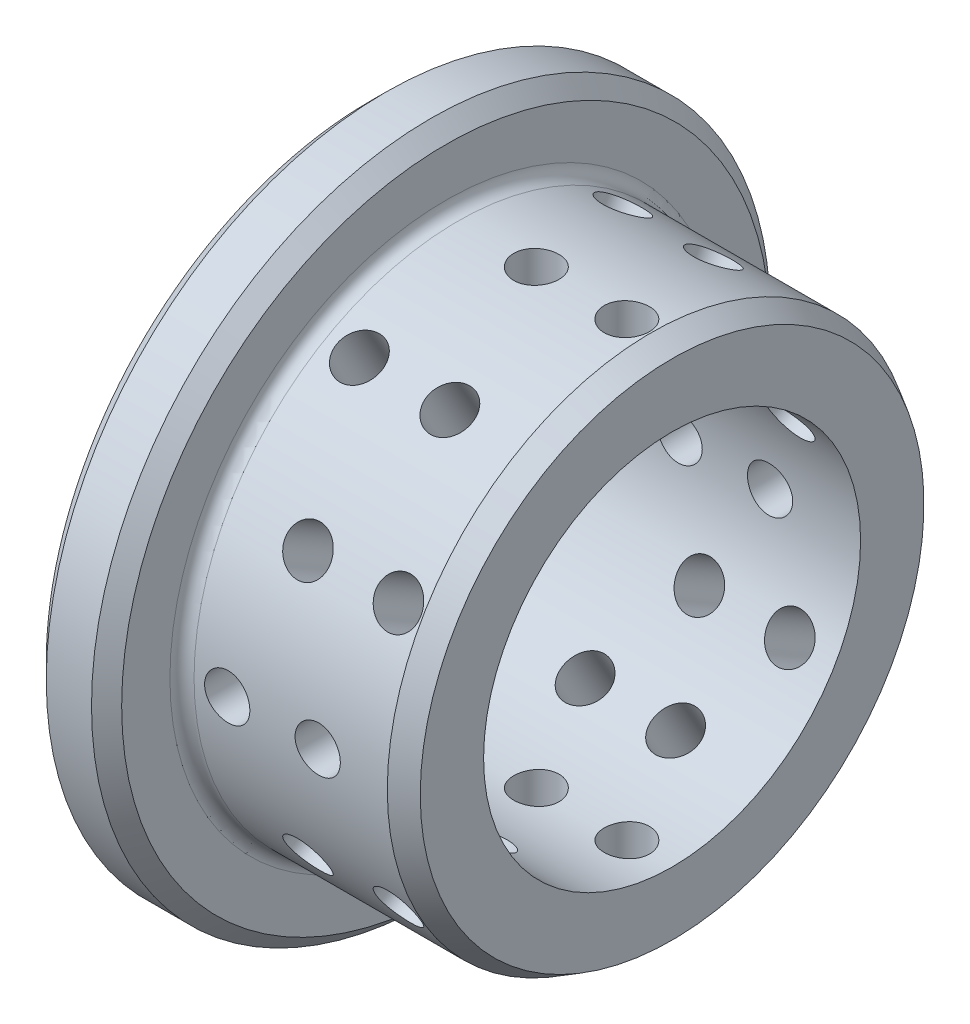
SolidWorks part; units mm, degrees
material "Cast Alloy Steel"
ref_plane "Front Plane" through (0, 0, 0) normal (0, 0, 1) x (1, 0, 0)
ref_plane "Top Plane" through (0, 0, 0) normal (0, 1, 0) x (1, 0, 0)
ref_plane "Right Plane" through (0, 0, 0) normal (1, 0, 0) x (0, 0, -1)
sketch "Sketch1" plane through (0, 0, 0) normal (0, 0, 1) x (1, 0, 0)
  line L0 (0, 0) -> (27.5999, 0) construction
  line L1 (0, 12.5) -> (0, 22.5)
  line L2 (0, 22.5) -> (5, 22.5)
  line L3 (5, 22.5) -> (5, 17.5)
  line L4 (5, 17.5) -> (20, 17.5)
  line L5 (20, 17.5) -> (20, 12.5)
  line L6 (20, 12.5) -> (0, 12.5)
  dimension "D1" = 45
  dimension "D2" = 35
  dimension "D3" = 25
  dimension "D4" = 5
  dimension "D5" = 15
revolve "Revolve1" add sketch "Sketch1" angle 360 about L0
sketch "Sketch2" plane through (0, 0, 0) normal (-1, 0, 0) x (0, 0, 1)
  circle A0 centre (0, 0) radius 20 construction
  circle A1 centre (0, 20) radius 1.5
  circle A2 centre (17.3205, 10) radius 1.5
  circle A3 centre (17.3205, -10) radius 1.5
  circle A4 centre (0, -20) radius 1.5
  circle A5 centre (-17.3205, -10) radius 1.5
  circle A6 centre (-17.3205, 10) radius 1.5
  point P17 (0, 0)
  dimension "D1" = 40
  dimension "D2" = 3
  dimension "D3" = 6
extrude "Cut-Extrude1" cut sketch "Sketch2" against normal blind 4 and the other way through all
sketch "Sketch3" plane through (0, 0, 0) normal (-1, 0, 0) x (0, 0, 1)
  line L0 (0, 0) -> (17, 0) construction
  circle A0 centre (0, 0) radius 17 construction
  circle A1 centre (17, 0) radius 1.5
  dimension "D1" = 34
  dimension "D2" = 3
extrude "Cut-Extrude2" cut sketch "Sketch3" against normal blind 4
pattern_circular "CirPattern1" count 6 over 360 about axis through (0, 0, 0) along (-1, 0, 0) of "Cut-Extrude2"
sketch "Sketch4" plane through (0, 0, 0) normal (0, 1, 0) x (1, 0, 0)
  line L0 (0, 0) -> (20, 0) construction
  line L1 (20, -17.5) -> (20, 17.5) construction
  circle A0 centre (11, 0) radius 1.5
  circle A1 centre (17, 0) radius 1.5
  dimension "D3" = 3
  dimension "D1" = 3
  dimension "D2" = 6
extrude "Cut-Extrude3" cut sketch "Sketch4" against normal up to surface (17.4356 mm away) up to face at (5, 0, 17.5)
sketch "Sketch5" plane through (0, 0, 0) normal (0, 0, 1) x (1, 0, 0)
  line L0 (0, 0) -> (20, 0) construction
  line L1 (20, -17.5) -> (20, 17.5) construction
  circle A0 centre (8, 0) radius 1.5
  circle A1 centre (14, 0) radius 1.5
  dimension "D2" = 3
  dimension "D1" = 8
  dimension "D3" = 6
extrude "Cut-Extrude4" cut sketch "Sketch5" against normal up to surface (17.5 mm away) up to face at (11.3388, -17.4389, -1.4612)
pattern_circular "CirPattern2" count 6 over 360 about axis through (0, 0, 0) along (-1, 0, 0) of "Cut-Extrude4", "Cut-Extrude3"
chamfer "Chamfer1" distance 0.8 angle 60 1 edges at (20, 0, 17.5) first distance on face at (20, 0, 17.5)
fillet "Fillet1" radius 0.8 1 edges at (5, 0, 17.5)
chamfer "Chamfer2" distance 1 angle 45 2 edges at (5, 0, 22.5) (0, 0, 22.5)
